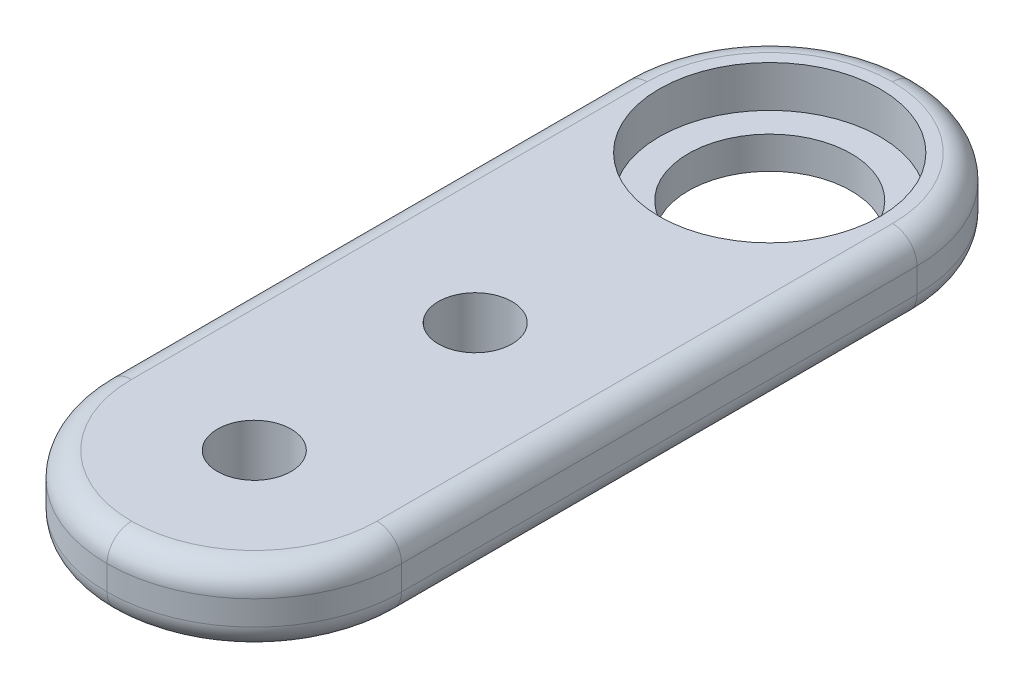
SolidWorks part; units mm, degrees
material "6061 Alloy"
ref_plane "Front Plane" through (0, 0, 0) normal (0, 0, 1) x (1, 0, 0)
ref_plane "Top Plane" through (0, 0, 0) normal (0, 1, 0) x (1, 0, 0)
ref_plane "Right Plane" through (0, 0, 0) normal (1, 0, 0) x (0, 0, -1)
sketch "Sketch1" plane through (0, 0, 0) normal (0, 1, 0) x (1, 0, 0)
  line L0 (0, 34.925) -> (0, -34.925) construction
  line L1 (-12.7, -34.925) -> (12.7, -34.925)
  line L2 (-12.7, -34.925) -> (-12.7, 34.925)
  line L3 (-12.7, 34.925) -> (12.7, 34.925)
  line L4 (12.7, -34.925) -> (12.7, 34.925)
  line L5 (-12.7, -34.925) -> (12.7, 34.925) construction
  line L6 (-12.7, 34.925) -> (12.7, -34.925) construction
  circle A1 centre (0, -3.175) radius 3.175
  circle A2 centre (0, -22.225) radius 3.175
  point P0 (0, 0)
  point P8 (0, 22.225)
  dimension "D3" = 25.4
  dimension "D2" = 12.7
  dimension "D6" = 6.35
  dimension "D1" = 25.4
  dimension "D4" = 19.05
  dimension "D5" = 12.7
extrude "Boss-Extrude1" add sketch "Sketch1" along normal blind 6.35
fillet "Fillet1" radius 12.7 4 edges at (-12.7, 3.175, -34.925) (12.7, 3.175, -34.925) (-12.7, 3.175, 34.925) (12.7, 3.175, 34.925)
fillet "Fillet2" radius 2.1167 12 edges at (8.9803, 0, 31.2053) (12.7, 0, 0) (8.9803, 0, -31.2053) (-8.9803, 0, -31.2053) (-12.7, 0, 0) (-8.9803, 6.35, -31.2053) (8.9803, 6.35, -31.2053) (12.7, 6.35, 0) (8.9803, 6.35, 31.2053) (-8.9803, 6.35, 31.2053) (-8.9803, 0, 31.2053) (-12.7, 6.35, 0)
ref_plane "Plane1" through (0, 0, 0) normal (-1, 0, 0) x (0, 0, 1)
sketch "Sketch3" plane through (0, 0, 0) normal (-1, 0, 0) x (0, 0, 1)
  line L0 (-22.225, 0) -> (-22.225, 6.35)
  line L1 (-31.75, 6.35) -> (-31.75, 2.7781)
  line L2 (-22.225, 6.35) -> (-32.8083, 6.35) construction
  line L3 (-31.75, 2.7781) -> (-22.225, 2.7781)
  line L5 (-29.2418, 2.7781) -> (-29.2418, 0)
  line L6 (34.925, 0) -> (-34.925, 0) construction
  line L7 (-29.2418, 0) -> (-22.225, 0) construction
  line L8 (-22.225, 6.35) -> (-31.75, 6.35) construction
  line L9 (-31.75, 6.35) -> (-31.75, 9.9219)
  line L10 (-31.75, 9.9219) -> (-22.225, 9.9219)
  line L11 (-22.225, 9.9219) -> (-22.225, 6.35)
  line L12 (-22.225, 9.9219) -> (-25.7593, -6.7056) construction
  line L13 (-20.2508, -3.8797) -> (-29.6422, -1.8835)
  line L14 (-29.6422, -1.8835) -> (-28.6513, 2.7781)
  line L15 (-22.225, 0) -> (-22.225, -3.4601)
  line L16 (-29.6422, -1.8835) -> (-34.4188, -0.8682) construction
  point P19 (-24.9465, -2.8816)
  dimension "D1" = 3.5719
  dimension "D2" = 12
  dimension "D3" = 9.6012
  dimension "D4" = 9.525
  dimension "D5" = 4.7658
sketch "Sketch5" plane through (0, 6.35, 0) normal (0, 1, 0) x (1, 0, 0)
  circle A0 centre (0, 22.225) radius 9.525
  circle A1 centre (0, 22.225) radius 7.0168
extrude "Cut-Extrude2" cut sketch "Sketch5" against normal up to vertex (3.5719 mm away) up to point (0, 2.7781, -31.75)
extrude "Cut-Extrude3" cut sketch "Sketch5<2>" against normal up to vertex (6.35 mm away) contours A1 region at (0, 6.35, -22.225) up to point (0, 0, -29.2418)
sketch "Sketch5<2>" plane through (0, 6.35, 0) normal (0, 1, 0) x (1, 0, 0) same geometry as "Sketch5"
